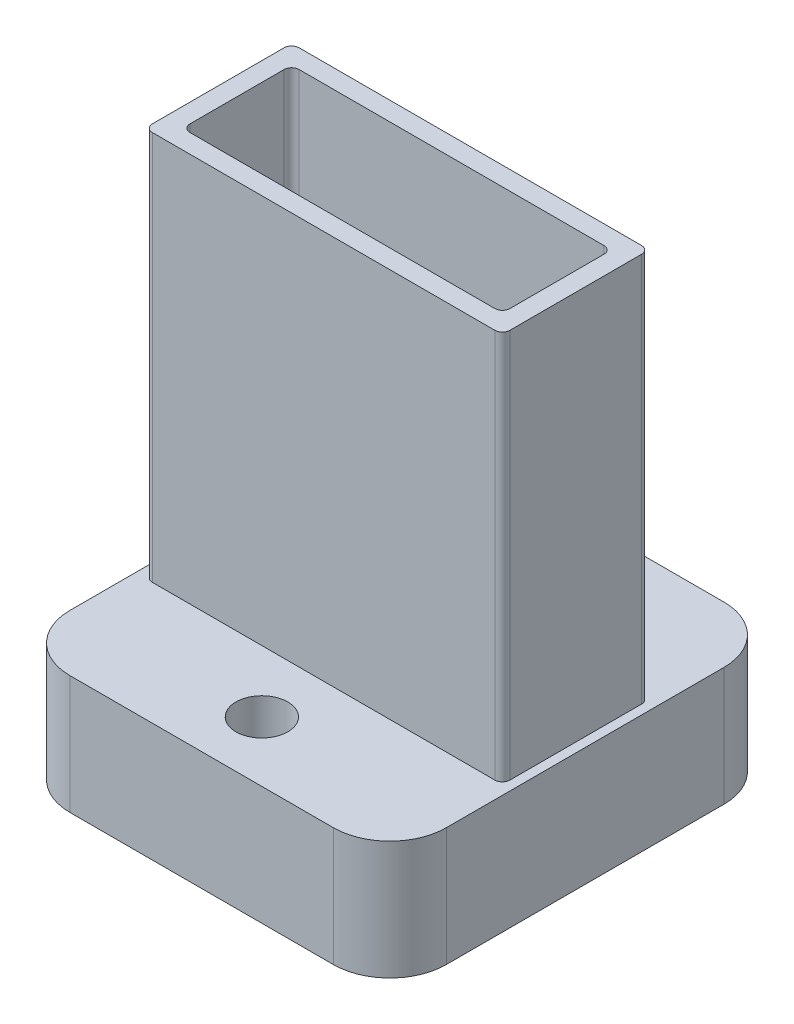
SolidWorks part; units mm, degrees
ref_plane "Front Plane" through (0, 0, 0) normal (0, 0, 1) x (1, 0, 0)
ref_plane "Top Plane" through (0, 0, 0) normal (0, 1, 0) x (1, 0, 0)
ref_plane "Right Plane" through (0, 0, 0) normal (1, 0, 0) x (0, 0, -1)
sketch "Sketch1" plane through (0, 0, 0) normal (0, 1, 0) x (1, 0, 0)
  line L0 (11.557, 4.953) -> (-11.557, 4.953)
  line L7 (-12.065, -4.445) -> (-12.065, 4.445)
  line L8 (11.557, -4.953) -> (-11.557, -4.953)
  line L9 (12.065, -4.445) -> (12.065, 4.445)
  arc A0 (11.557, -4.953) -> (12.065, -4.445) centre (11.557, -4.445) ccw
  arc A1 (11.557, 4.953) -> (12.065, 4.445) centre (11.557, 4.445) cw
  arc A2 (-12.065, -4.445) -> (-11.557, -4.953) centre (-11.557, -4.445) ccw
  arc A3 (-11.557, 4.953) -> (-12.065, 4.445) centre (-11.557, 4.445) ccw
  point P0 (0, 0)
  point P10 (0, 0)
  point P19 (0, 0)
extrude "Boss-Extrude1" add sketch "Sketch1" along normal blind 23.622
sketch "Sketch2" plane through (0, 23.622, 0) normal (0, 1, 0) x (1, 0, 0)
  line L0 (11.557, 4.953) -> (-11.557, 4.953)
  line L1 (10.287, -3.683) -> (-10.287, -3.683)
  line L2 (10.795, -3.175) -> (10.795, 3.175)
  line L3 (10.287, 3.683) -> (-10.287, 3.683)
  line L4 (-10.795, -3.175) -> (-10.795, 3.175)
  line L5 (10.795, -3.683) -> (-10.795, 3.683) construction
  line L6 (10.795, 3.683) -> (-10.795, -3.683) construction
  line L7 (-12.065, -4.445) -> (-12.065, 4.445)
  line L8 (11.557, -4.953) -> (-11.557, -4.953)
  line L9 (12.065, -4.445) -> (12.065, 4.445)
  line L10 (12.065, -4.953) -> (-12.065, -4.953) construction
  line L11 (12.065, -4.953) -> (12.065, 4.953) construction
  line L12 (12.065, 4.953) -> (-12.065, 4.953) construction
  line L13 (10.795, -3.683) -> (-10.795, -3.683) construction
  line L14 (10.795, -3.683) -> (10.795, 3.683) construction
  line L15 (10.795, 3.683) -> (-10.795, 3.683) construction
  line L16 (-10.795, -3.683) -> (-10.795, 3.683) construction
  line L17 (-12.065, -4.953) -> (-12.065, 4.953) construction
  arc A0 (11.557, -4.953) -> (12.065, -4.445) centre (11.557, -4.445) ccw
  arc A1 (11.557, 4.953) -> (12.065, 4.445) centre (11.557, 4.445) cw
  arc A2 (10.287, -3.683) -> (10.795, -3.175) centre (10.287, -3.175) ccw
  arc A3 (10.795, 3.175) -> (10.287, 3.683) centre (10.287, 3.175) ccw
  arc A4 (-10.287, 3.683) -> (-10.795, 3.175) centre (-10.287, 3.175) ccw
  arc A5 (-10.287, -3.683) -> (-10.795, -3.175) centre (-10.287, -3.175) cw
  arc A6 (-12.065, -4.445) -> (-11.557, -4.953) centre (-11.557, -4.445) ccw
  arc A7 (-11.557, 4.953) -> (-12.065, 4.445) centre (-11.557, 4.445) ccw
  point P0 (0, 0)
  point P10 (0, 0)
  dimension "D4" = 0.508
  dimension "D1" = 21.59
  dimension "D2" = 7.366
  dimension "D3" = 1.27
extrude "Boss-Extrude2" add sketch "Sketch2" along normal blind 10.668
sketch "Sketch4" plane through (0, 0, 0) normal (0, 1, 0) x (1, 0, 0)
  line L3 (-8.89, -13.184) -> (8.89, -13.184)
  line L5 (-8.271, 0) -> (6.4954, 0) construction
  line L6 (-8.89, 13.184) -> (8.89, 13.184)
  line L10 (-12.7, 9.374) -> (-12.7, -9.374)
  line L11 (12.7, 9.374) -> (12.7, -9.374)
  circle A0 centre (0, -9.12) radius 1.75
  arc A1 (8.89, -13.184) -> (12.7, -9.374) centre (8.89, -9.374) ccw
  arc A2 (-12.7, -9.374) -> (-8.89, -13.184) centre (-8.89, -9.374) ccw
  circle A3 centre (0, 9.12) radius 1.75
  arc A4 (8.89, 13.184) -> (12.7, 9.374) centre (8.89, 9.374) cw
  arc A5 (-12.7, 9.374) -> (-8.89, 13.184) centre (-8.89, 9.374) cw
  dimension "D1" = 3.5
  dimension "D4" = 3.81
  dimension "D3" = 4.064
extrude "Boss-Extrude3" add sketch "Sketch4" along normal blind 8
